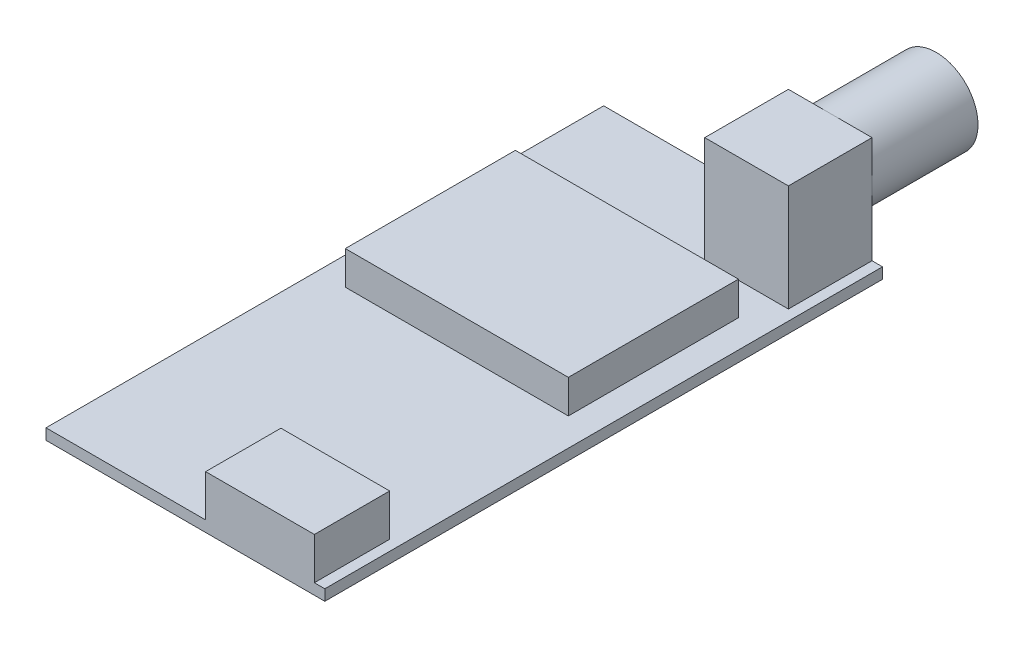
SolidWorks part; units mm, degrees
note: The reader was unsure of these and kept them because the rebuilt part matched: shared geometry of "Sketch4<3>".
ref_plane "Front Plane" through (0, 0, 0) normal (0, 0, 1) x (1, 0, 0)
ref_plane "Top Plane" through (0, 0, 0) normal (0, 1, 0) x (1, 0, 0)
ref_plane "Right Plane" through (0, 0, 0) normal (1, 0, 0) x (0, 0, -1)
sketch "Sketch1" plane through (0, 0, 0) normal (0, 1, 0) x (1, 0, 0)
  line L0 (-10, 0) -> (10, 0)
  line L1 (-10, 0) -> (-10, -40)
  line L2 (-10, -40) -> (10, -40)
  line L3 (10, -40) -> (10, 0)
  point P0 (10, -24.2574)
  point P4 (0, 0)
  dimension "D1" = 20
  dimension "D2" = 40
extrude "Boss-Extrude1" add sketch "Sketch1" along normal blind 0.78
sketch "Sketch4" plane through (0, 0, 0) normal (0, 0, 1) x (1, 0, 0)
  line L0 (-10, 0.78) -> (10, 0.78) construction
  line L1 (-10, 0.78) -> (10, 0.78)
  line L2 (3.25, 8.43) -> (9.25, 8.43)
  line L3 (3.25, 8.43) -> (3.25, 0.78)
  line L4 (3.25, 0.78) -> (9.25, 0.78)
  line L5 (9.25, 8.43) -> (9.25, 0.78)
  line L6 (3.25, 8.43) -> (9.25, 0.78) construction
  line L7 (3.25, 0.78) -> (9.25, 8.43) construction
  line L8 (10, 0.78) -> (10, 0) construction
  line L9 (3.25, 8.43) -> (9.25, 8.43)
  line L10 (3.25, 8.43) -> (3.25, 2.43)
  line L11 (3.25, 2.43) -> (9.25, 2.43)
  line L12 (9.25, 8.43) -> (9.25, 2.43)
  circle A0 centre (6.25, 5.43) radius 3
  point P3 (6.25, 4.605)
  point P8 (2.7019, 1.511)
  point P11 (0, 5.3449)
  point P12 (0, 0)
  point P15 (0, 4.605)
  dimension "D1" = 7.65
  dimension "D2" = 6
  dimension "D3" = 6
  dimension "D4" = 0.75
extrude "Boss-Extrude2" add sketch "Sketch4" along normal blind 6 contours L3 L11 L5 L2 | L11 L3 L1 L5 | A0 | A0 L2 L3 | A0 L10 L11 | A0 L11 L12
extrude "Boss-Extrude3" add sketch "Sketch4<3>" against normal blind 7.6 contours A0
sketch "Sketch4<3>" plane through (0, 0, 0) normal (0, 0, 1) x (1, 0, 0) same geometry as "Sketch4"
sketch "Sketch5" plane through (0, 0.78, 0) normal (0, 1, 0) x (1, 0, 0)
  line L0 (-10, -40) -> (10, -40) construction
  line L1 (1.45, -40) -> (9.25, -40)
  line L2 (1.45, -40) -> (1.45, -34.6)
  line L3 (1.45, -34.6) -> (9.25, -34.6)
  line L4 (9.25, -40) -> (9.25, -34.6)
  line L5 (10, -40) -> (10, 0) construction
  point P6 (9.2763, -40)
  dimension "D1" = 7.8
  dimension "D2" = 5.4
  dimension "D3" = 0.75
extrude "Boss-Extrude4" add sketch "Sketch5" along normal blind 3
sketch "Sketch6" plane through (0, 0.78, 0) normal (0, 1, 0) x (1, 0, 0)
  line L1 (-8, -8.333) -> (8, -8.333)
  line L2 (-8, -8.333) -> (-8, -20.533)
  line L3 (-8, -20.533) -> (8, -20.533)
  line L4 (8, -8.333) -> (8, -20.533)
  line L5 (-8, -8.333) -> (8, -20.533) construction
  line L6 (-8, -20.533) -> (8, -8.333) construction
  point P0 (0, -14.433)
  point P5 (0, -20.5151)
  point P7 (0, -14.433)
  point P8 (0, 0)
  point P9 (0, 0)
  dimension "D1" = 12.2
  dimension "D2" = 16
extrude "Boss-Extrude5" add sketch "Sketch6" along normal blind 2.4
equation "\"D1@Boss-Extrude3\"=7.6"
